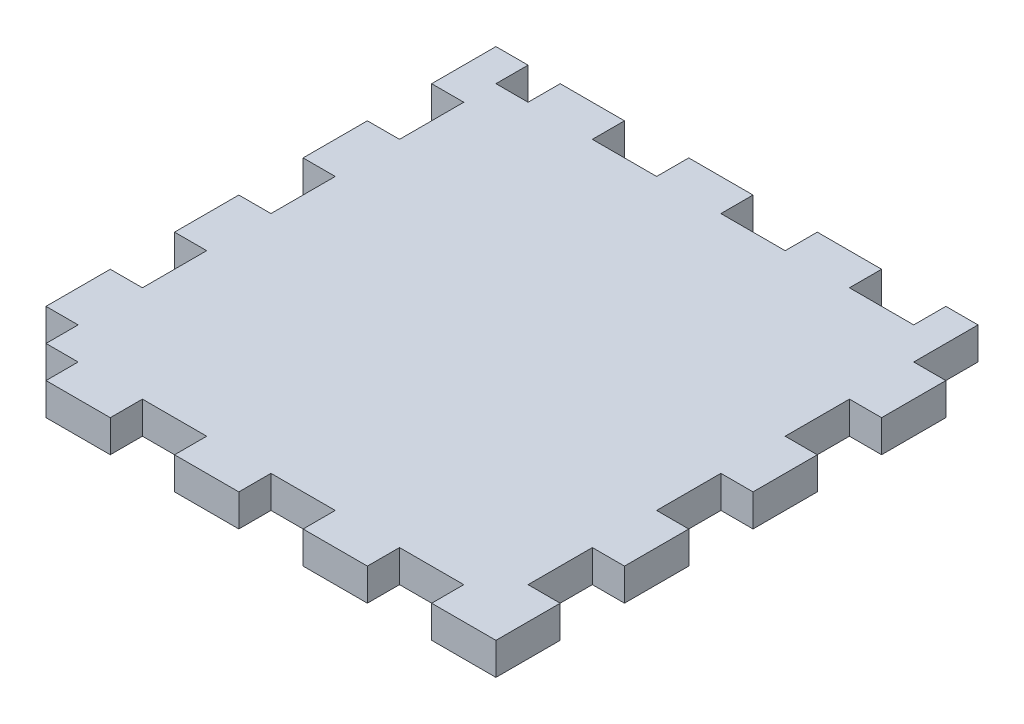
SolidWorks part; units mm, degrees
material "Acrylic (Medium-high impact)"
ref_plane "Front Plane" through (0, 0, 0) normal (0, 0, 1) x (1, 0, 0)
ref_plane "Top Plane" through (0, 0, 0) normal (0, 1, 0) x (1, 0, 0)
ref_plane "Right Plane" through (0, 0, 0) normal (1, 0, 0) x (0, 0, -1)
sketch "Sketch1" plane through (0, 0, 0) normal (0, 1, 0) x (1, 0, 0)
  line L1 (0, 0) -> (101.6, 0)
  line L2 (0, 0) -> (0, 101.6)
  line L3 (0, 101.6) -> (101.6, 101.6)
  line L4 (101.6, 0) -> (101.6, 101.6)
  dimension "D1" = 101.6
  dimension "D2" = 101.6
extrude "Boss-Extrude1" add sketch "Sketch1" along normal blind 6.35
ref_plane "Plane1" through (0, 0, -50.8) normal (0, 0, -1) x (-1, 0, 0)
ref_plane "Plane2" through (50.8, 0, 0) normal (-1, 0, 0) x (0, 0, 1)
sketch "Sketch2" plane through (0, 6.35, 0) normal (0, 1, 0) x (1, 0, 0)
  line L0 (6.35, 101.6) -> (6.35, 0)
  line L1 (101.6, 101.6) -> (0, 101.6) construction
  line L2 (0, 0) -> (101.6, 0) construction
  line L3 (0, 95.25) -> (101.6, 95.25)
  line L4 (0, 101.6) -> (0, 0) construction
  line L5 (101.6, 0) -> (101.6, 101.6) construction
  line L6 (12.7, 101.6) -> (12.7, 95.25)
  line L7 (0, 12.7) -> (6.35, 12.7)
  line L8 (0, 25.4) -> (6.35, 25.4)
  line L9 (0, 38.1) -> (6.35, 38.1)
  line L10 (0, 50.8) -> (6.35, 50.8)
  line L11 (0, 63.5) -> (6.35, 63.5)
  line L12 (0, 76.2) -> (6.35, 76.2)
  line L13 (0, 88.9) -> (6.35, 88.9)
  line L14 (0, 101.6) -> (6.35, 101.6)
  line L15 (25.4, 101.6) -> (25.4, 95.25)
  line L16 (38.1, 101.6) -> (38.1, 95.25)
  line L17 (50.8, 101.6) -> (50.8, 95.25)
  line L18 (63.5, 101.6) -> (63.5, 95.25)
  line L19 (76.2, 101.6) -> (76.2, 95.25)
  line L20 (88.9, 101.6) -> (88.9, 95.25)
  line L21 (101.6, 101.6) -> (101.6, 95.25)
  line L22 (95.25, 101.6) -> (95.25, 0)
  line L23 (95.25, 12.7) -> (101.6, 12.7)
  line L24 (95.25, 25.4) -> (101.6, 25.4)
  line L25 (95.25, 38.1) -> (101.6, 38.1)
  line L26 (0, 101.6) -> (0, 0)
  line L27 (0, 0) -> (101.6, 0)
  line L28 (101.6, 0) -> (101.6, 101.6)
  line L29 (101.6, 101.6) -> (0, 101.6)
  line L30 (0, 101.6) -> (0, 0)
  line L31 (0, 0) -> (101.6, 0)
  line L32 (101.6, 0) -> (101.6, 101.6)
  line L33 (101.6, 101.6) -> (0, 101.6)
  line L34 (95.25, 50.8) -> (101.6, 50.8)
  line L35 (95.25, 63.5) -> (101.6, 63.5)
  line L36 (95.25, 76.2) -> (101.6, 76.2)
  line L37 (95.25, 88.9) -> (101.6, 88.9)
  line L38 (95.25, 101.6) -> (101.6, 101.6)
  line L39 (0, 6.35) -> (101.6, 6.35)
  line L40 (12.7, 6.35) -> (12.7, 0)
  line L41 (25.4, 6.35) -> (25.4, 0)
  line L42 (38.1, 6.35) -> (38.1, 0)
  line L43 (50.8, 6.35) -> (50.8, 0)
  line L44 (63.5, 6.35) -> (63.5, 0)
  line L45 (76.2, 6.35) -> (76.2, 0)
  line L46 (88.9, 6.35) -> (88.9, 0)
  line L47 (101.6, 6.35) -> (101.6, 0)
  line M5 (0, 101.6) -> (0, 0)
  line M6 (0, 0) -> (101.6, 0)
  line M7 (101.6, 0) -> (101.6, 101.6)
  line M8 (101.6, 101.6) -> (0, 101.6)
  dimension "D1" = 6.35
  dimension "D2" = 6.35
  dimension "D3" = 12.7
  dimension "D4" = 12.7
  dimension "D7" = 6.35
  dimension "D8" = 12.7
  dimension "D10" = 6.35
  dimension "D11" = 12.7
  dimension "D6" = 0
  dimension "D5" = 8
  dimension "D9" = 8
extrude "Cut-Extrude1" cut sketch "Sketch2" against normal through all contours L22 L37 L3 M7 | L22 L3 M8 M7 | L36 L22 L35 M7 | L34 L22 L25 M7 | L24 L22 L23 M7 | L7 L0 M5 M6 | L9 L8 L0 M5 | L11 L10 L0 M5 | L13 L12 L0 M5 region at (3.175, 6.35, -82.55) region at (3.175, 6.35, -57.15) region at (3.175, 6.35, -31.75) region at (3.175, 6.35, -9.525) region at (98.425, 6.35, -98.425) region at (98.425, 6.35, -92.075) region at (98.425, 6.35, -69.85) region at (98.425, 6.35, -44.45) region at (98.425, 6.35, -19.05)
extrude "Cut-Extrude2" cut sketch "Sketch2<3>" against normal blind 6.35 contours L6 L0 L3 M8 | L16 L15 L3 M8 | L18 L17 L3 M8 | L20 L19 L3 M8 | L46 L39 L45 M6 | L44 L39 L43 M6 | L42 L39 L41 M6 | L40 L39 L0 M6 | L39 L30 L0 M6 region at (9.525, 6.35, -98.425) region at (31.75, 6.35, -98.425) region at (57.15, 6.35, -98.425) region at (9.525, 6.35, -3.175) region at (3.175, 6.35, -3.175) region at (82.55, 6.35, -98.425) region at (31.75, 6.35, -3.175) region at (57.15, 6.35, -3.175) region at (82.55, 6.35, -3.175)
sketch "Sketch2<3>" plane through (0, 6.35, 0) normal (0, 1, 0) x (1, 0, 0) same geometry as "Sketch2"
mirror "Mirror2" [suppressed] about plane through (0, 0, -50.8) normal (0, 0, -1)
equation "\"acrillic thick\"= 0.25"
equation "\"D1@Boss-Extrude1\"=\"acrillic thick\""
equation "\"D1@Sketch2\"=\"acrillic thick\""
equation "\"D2@Sketch2\"=\"acrillic thick\""
equation "\"D7@Sketch2\"=\"acrillic thick\""
equation "\"D10@Sketch2\"=\"acrillic thick\""
